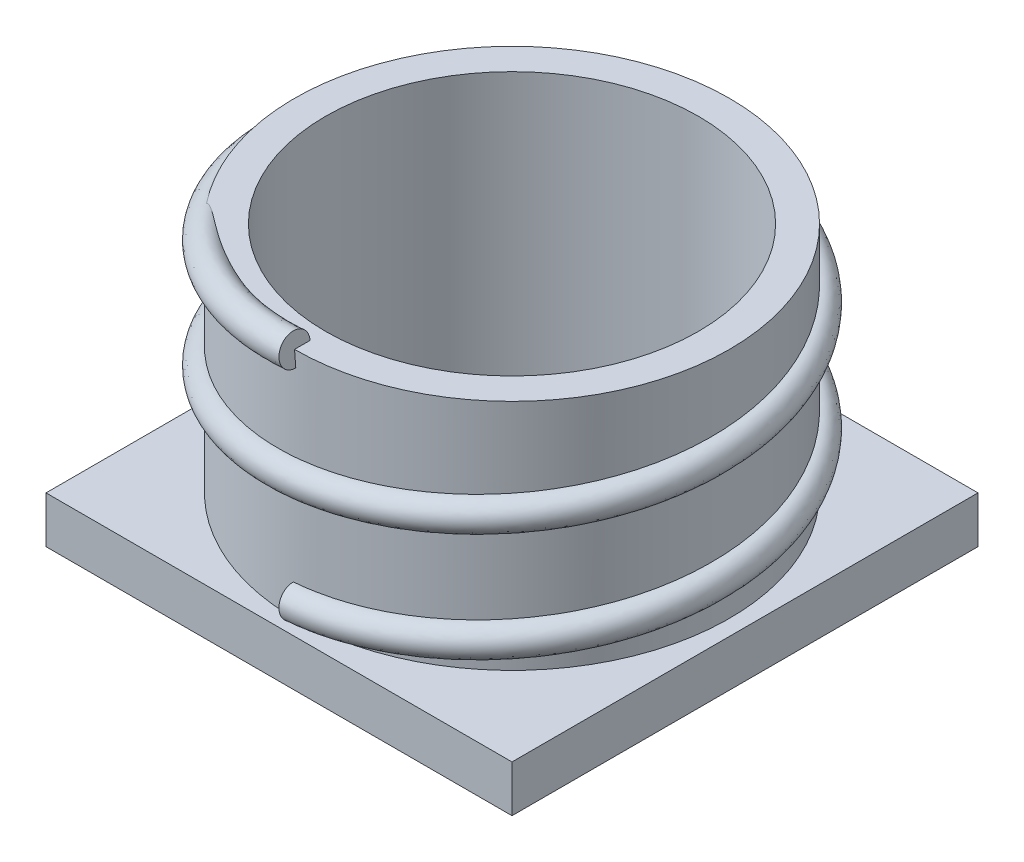
SolidWorks part; units mm, degrees
ref_plane "Front" through (0, 0, 0) normal (0, 0, 1) x (1, 0, 0)
ref_plane "Top" through (0, 0, 0) normal (0, 1, 0) x (1, 0, 0)
ref_plane "Right" through (0, 0, 0) normal (1, 0, 0) x (0, 0, -1)
sketch "Sketch1" plane through (0, 0, 0) normal (0, 1, 0) x (1, 0, 0)
  line L1 (-19.05, -19.05) -> (19.05, -19.05)
  line L2 (-19.05, -19.05) -> (-19.05, 19.05)
  line L3 (-19.05, 19.05) -> (19.05, 19.05)
  line L4 (19.05, -19.05) -> (19.05, 19.05)
extrude "Boss-Extrude1" add sketch "Sketch1" along normal blind 3.81
sketch "Sketch2" plane through (0, 3.81, 0) normal (0, 1, 0) x (1, 0, 0)
  circle A0 centre (0, 0) radius 17.78
extrude "Boss-Extrude2" add sketch "Sketch2" along normal blind 19.05
sketch "Sketch3" plane through (0, 22.86, 0) normal (0, 1, 0) x (1, 0, 0)
  circle A0 centre (0, 0) radius 15.24
extrude "Cut-Extrude1" cut sketch "Sketch3" against normal through all
ref_plane "Plane2" through (0, 22.86, 0) normal (0, 1, 0) x (1, 0, 0)
sketch "Sketch4" plane through (0, 22.86, 0) normal (0, 1, 0) x (1, 0, 0)
  circle A0 centre (0, 0) radius 17.78
curve "Helix/Spiral1" pitch 8.89 height 17.78 radius 17.78 centre (0, 22.86, 0) axis (0, -1, 0) start towards (0, 0, 1)
ref_plane "Plane3" through (0, 0, 0) normal (1, 0, 0) x (0, 0, -1)
ref_plane "Plane4" through (0, 0, 0) normal (0, 0, -1) x (-1, 0, 0)
ref_axis "Axis3" through (0, 36.9578, 0) along (0, -1, 0)
sketch "Sketch9" plane through (0, 0, 0) normal (1, 0, 0) x (0, 0, -1)
  line L2 (19.558, 22.86) -> (-19.558, 22.86) construction
  line L4 (-18.678, 22.86) -> (-17.78, 22.86)
  line L5 (-18.678, 22.86) -> (-17.78, 21.962)
  line L6 (-17.78, 22.86) -> (-17.78, 3.81) construction
  line L7 (-17.78, 22.86) -> (-17.78, 21.962)
  spline S1 degree 3 poles (-17.78, 22.86) (-17.78, 22.7006) (-17.0898, 22.3791) (-14.102, 21.899) (-9.5031, 21.4184) (-3.8186, 20.9378) (2.3022, 20.4573) (8.16, 19.9768) (13.0855, 19.4962) (16.5161, 19.0157) (18.0598, 18.5351) (17.5403, 18.0546) (15.0168, 17.5741) (10.7778, 17.0935) (5.3074, 16.613) (-0.7693, 16.1324) (-6.7581, 15.6519) (-11.9748, 15.1714) (-15.8235, 14.6908) (-17.8644, 14.2103) (-17.8644, 13.7297) (-15.8235, 13.2492) (-11.9748, 12.7686) (-6.7581, 12.2881) (-0.7693, 11.8076) (5.3074, 11.327) (10.7778, 10.8465) (15.0168, 10.3659) (17.5403, 9.8854) (18.0598, 9.4049) (16.5161, 8.9243) (13.0855, 8.4438) (8.16, 7.9632) (2.3022, 7.4827) (-3.8186, 7.0022) (-9.5031, 6.5216) (-14.102, 6.041) (-17.0898, 5.5609) (-17.78, 5.2394) (-17.78, 5.08) knots 0 0 0 0 0.027027 0.054054 0.081081 0.108108 0.135135 0.162162 0.189189 0.216216 0.243243 0.27027 0.297297 0.324324 0.351351 0.378378 0.405405 0.432432 0.459459 0.486486 0.513514 0.540541 0.567568 0.594595 0.621622 0.648649 0.675676 0.702703 0.72973 0.756757 0.783784 0.810811 0.837838 0.864865 0.891892 0.918919 0.945946 0.972973 1 1 1 1 construction
sweep "Sweep3" add path "Helix/Spiral1" circular profile diameter 2.54 parameters "D3"=2.54
